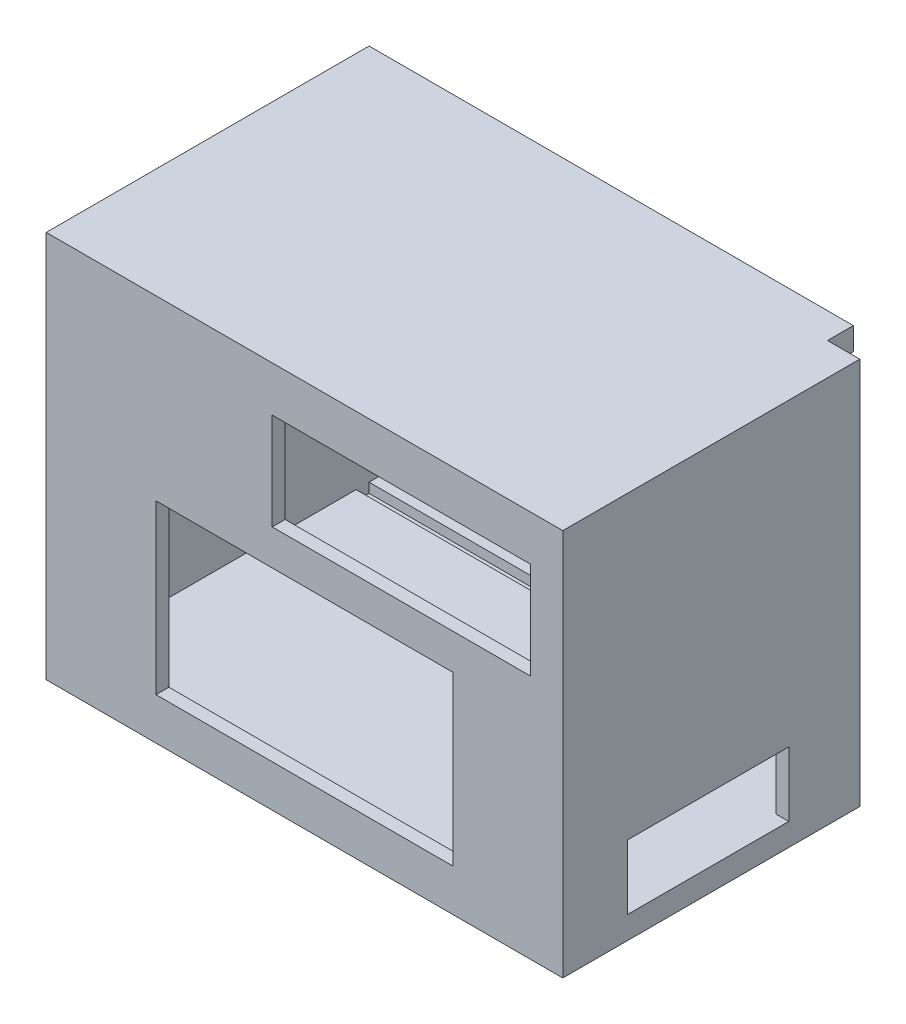
SolidWorks part; units mm, degrees
ref_plane "前视基准面" through (0, 0, 0) normal (0, 0, 1) x (1, 0, 0)
ref_plane "上视基准面" through (0, 0, 0) normal (0, 1, 0) x (1, 0, 0)
ref_plane "右视基准面" through (0, 0, 0) normal (1, 0, 0) x (0, 0, -1)
other "Configuration Table"
sketch "草图1" plane through (0, 0, 0) normal (0, 0, 1) x (1, 0, 0)
  line L1 (0, 0) -> (80, 0)
  line L2 (0, 0) -> (0, 60)
  line L3 (0, 60) -> (80, 60)
  line L4 (80, 0) -> (80, 60)
  line L5 (2, 3.5) -> (78, 3.5)
  line L6 (2, 3.5) -> (2, 56.5)
  line L7 (2, 56.5) -> (78, 56.5)
  line L8 (78, 3.5) -> (78, 56.5)
  line L9 (75, 53) -> (35, 53)
  line L10 (75, 53) -> (75, 38)
  line L11 (75, 38) -> (35, 38)
  line L12 (35, 53) -> (35, 38)
  line L13 (17, 32.5) -> (63, 32.5)
  line L14 (17, 32.5) -> (17, 6.5)
  line L15 (17, 6.5) -> (63, 6.5)
  line L16 (63, 32.5) -> (63, 6.5)
  line L17 (80, 0) -> (75, 0)
  line L18 (80, 0) -> (80, 60)
  line L19 (80, 60) -> (75, 60)
  line L20 (75, 0) -> (75, 60)
  line L21 (75, 58) -> (2, 58)
  line L22 (75, 58) -> (75, 2)
  line L23 (75, 2) -> (2, 2)
  line L24 (2, 58) -> (2, 2)
extrude "凸台-拉伸1" add sketch "草图1" along normal blind 50 contours L2 L1 L4 L3
extrude "切除-拉伸1" cut sketch "草图1<3>" along normal blind 48 contours L7 L8 L5 L6
sketch "草图1<3>" plane through (0, 0, 0) normal (0, 0, 1) x (1, 0, 0) same geometry as "草图1"
extrude "切除-拉伸2" cut sketch "草图1<4>" along normal blind 50 contours L11 L12 L9 L10
sketch "草图1<4>" plane through (0, 0, 0) normal (0, 0, 1) x (1, 0, 0) same geometry as "草图1"
extrude "切除-拉伸3" cut sketch "草图1<5>" along normal blind 50 contours L13 L16 L15 L14
sketch "草图1<5>" plane through (0, 0, 0) normal (0, 0, 1) x (1, 0, 0) same geometry as "草图1"
extrude "切除-拉伸5" cut sketch "草图1<7>" along normal blind 4 contours L20 L1 L4 L3 L7 L8 L5 region at (78.6277, 30, 0)
sketch "草图1<7>" plane through (0, 0, 0) normal (0, 0, 1) x (1, 0, 0) same geometry as "草图1"
ref_plane "基准面1" through (0, 0, 2) normal (0, 0, -1) x (-1, 0, 0)
extrude "切除-拉伸6" cut sketch "草图1<9>" along normal blind 2 from surface contours L21 L24 L23 L22 starting at plane "基准面1"
sketch "草图1<9>" plane through (0, 0, 0) normal (0, 0, 1) x (1, 0, 0) same geometry as "草图1"
ref_plane "基准面2" through (0, 0, 0) normal (-1, 0, 0) x (0, 0, 1)
sketch "草图2" plane through (0, 0, 0) normal (-1, 0, 0) x (0, 0, 1)
  line L1 (45, 56.5) -> (25, 56.5)
  line L2 (45, 56.5) -> (45, 36.5)
  line L3 (45, 36.5) -> (25, 36.5)
  line L4 (25, 56.5) -> (25, 36.5)
extrude "切除-拉伸7" cut sketch "草图2" against normal blind 2
ref_plane "基准面3" through (80, 0, 0) normal (1, 0, 0) x (0, 0, -1)
sketch "草图3" plane through (80, 0, 0) normal (1, 0, 0) x (0, 0, -1)
  line L1 (-40, 3.5) -> (-15, 3.5)
  line L2 (-40, 3.5) -> (-40, 13.5)
  line L3 (-40, 13.5) -> (-15, 13.5)
  line L4 (-15, 3.5) -> (-15, 13.5)
extrude "切除-拉伸8" cut sketch "草图3" against normal blind 2
